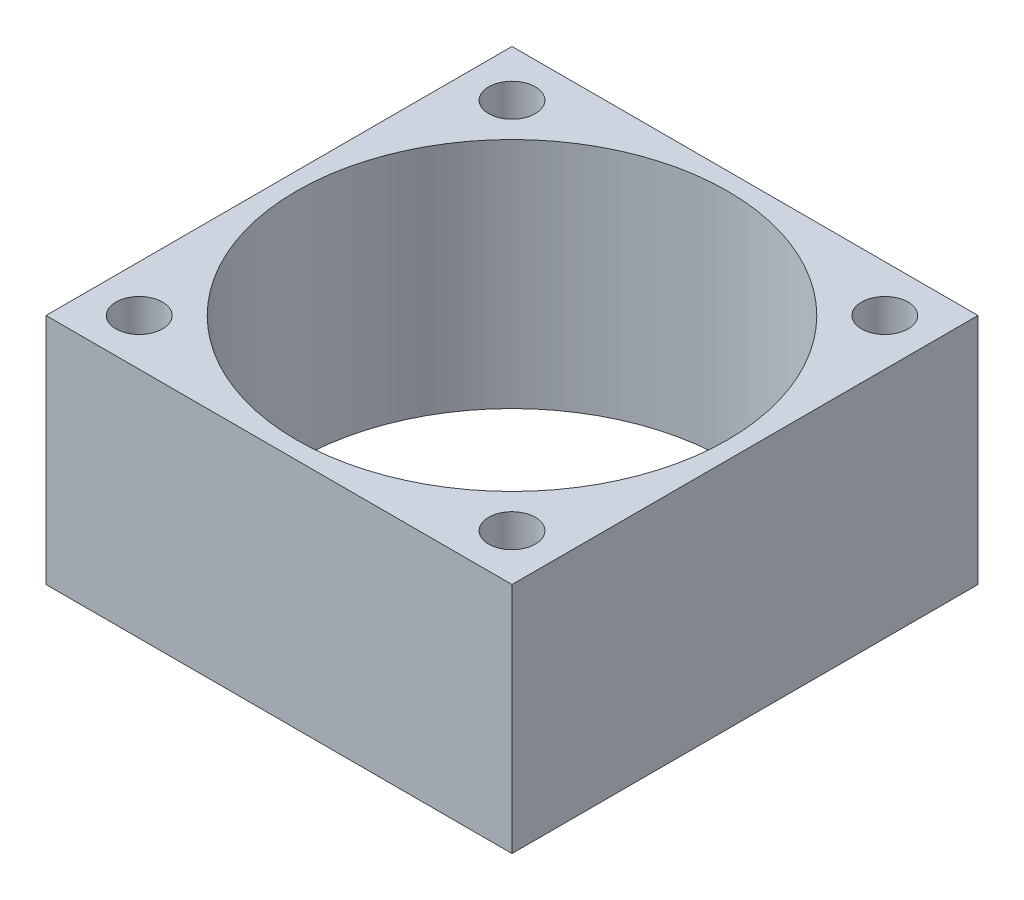
SolidWorks part; units mm, degrees
ref_plane "Front Plane" through (0, 0, 0) normal (0, 0, 1) x (1, 0, 0)
ref_plane "Top Plane" through (0, 0, 0) normal (0, 1, 0) x (1, 0, 0)
ref_plane "Right Plane" through (0, 0, 0) normal (1, 0, 0) x (0, 0, -1)
sketch "Sketch1" plane through (0, 0, 0) normal (0, 1, 0) x (1, 0, 0)
  line L1 (0, 0) -> (-40, 0)
  line L2 (0, 0) -> (0, -40)
  line L3 (0, -40) -> (-40, -40)
  line L4 (-40, 0) -> (-40, -40)
  dimension "D1" = 40
  dimension "D2" = 40
extrude "Boss-Extrude1" add sketch "Sketch1" along normal blind 20
sketch "Sketch2" plane through (0, 20, 0) normal (0, 1, 0) x (1, 0, 0)
  line L0 (-20, 0) -> (-20, -40) construction
  line L1 (0, 0) -> (-40, 0) construction
  line L2 (-40, -40) -> (0, -40) construction
  line L3 (-40, -20) -> (0, -20) construction
  line L4 (-40, 0) -> (-40, -40) construction
  line L5 (0, -40) -> (0, 0) construction
  line L6 (-34, -4) -> (-34, 0) construction
  line L7 (-6, -4) -> (-6, 0) construction
  line L8 (-38, -4) -> (-38, 0) construction
  line L9 (-36, -2) -> (-38, -2) construction
  line L10 (-4, -2) -> (-6, -2) construction
  line L11 (-2, -4) -> (-2, 0) construction
  circle A0 centre (-36, -4) radius 2
  circle A1 centre (-4, -4) radius 2
  circle A2 centre (-4, -36) radius 2
  circle A3 centre (-36, -36) radius 2
  circle A4 centre (-20, -20) radius 18.5
  dimension "D1" = 4
  dimension "D2" = 4
  dimension "D3" = 2
  dimension "D5" = 2
  dimension "D6" = 2
  dimension "D4" = 2
  dimension "D7" = 28
extrude "Cut-Extrude2" cut sketch "Sketch2" against normal up to surface (20 mm away) contours A1 | A0 | A3 | A2 | A4 up to face at (-20, 0, 20)
equation "\"CircleDiameter\"=4"
equation "\"D1@Sketch2\"=\"CircleDiameter\""
equation "\"D2@Sketch2\"=\"CircleDiameter\""
